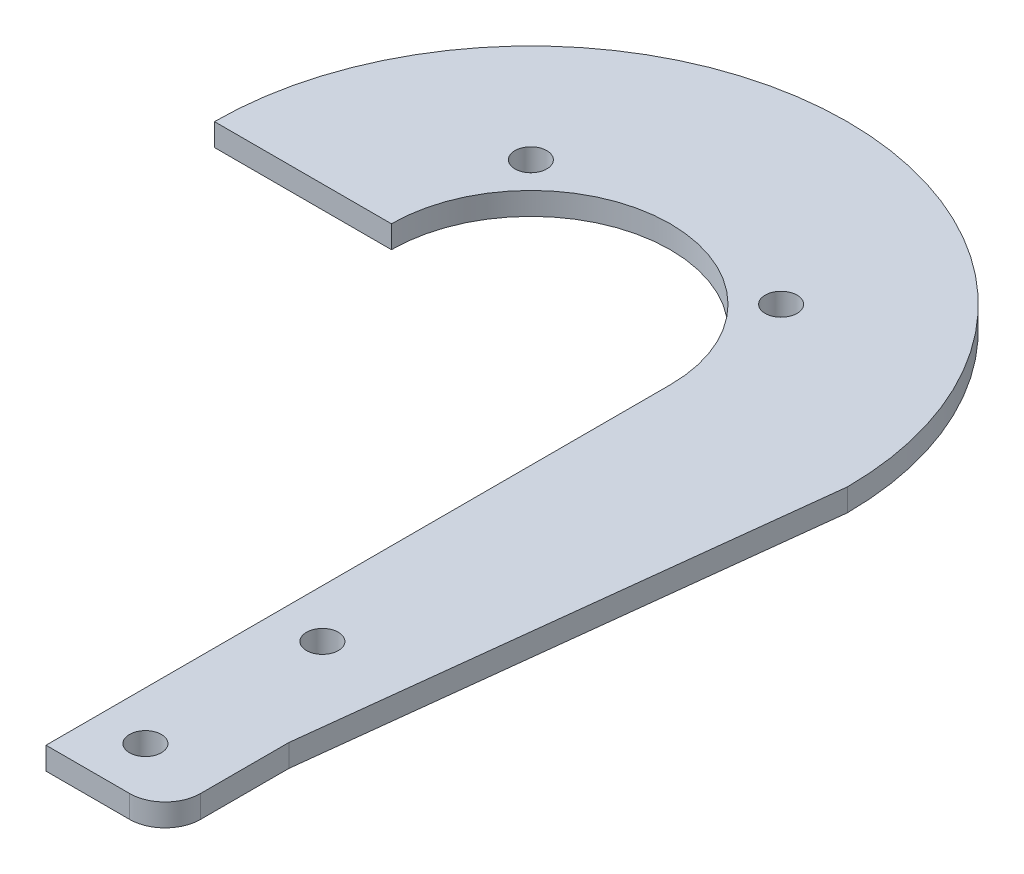
SolidWorks part; units mm, degrees
ref_plane "Front Plane" through (0, 0, 0) normal (0, 0, 1) x (1, 0, 0)
ref_plane "Top Plane" through (0, 0, 0) normal (0, 1, 0) x (1, 0, 0)
ref_plane "Right Plane" through (0, 0, 0) normal (1, 0, 0) x (0, 0, -1)
sketch "Sketch2" plane through (0, 0, 0) normal (0, 1, 0) x (1, 0, 0)
  line L0 (19.7, -88.2) -> (31.525, -88.2)
  line L1 (36.525, -83.2) -> (36.525, -70.7)
  line L2 (19.7, -88.2) -> (19.7, 0)
  line L3 (36.525, -70.7) -> (44.7, 0)
  line L4 (-44.7, 0) -> (-19.7, 0)
  line L5 (26.525, -80.975) -> (26.525, -55.975) construction
  line L6 (0, 0) -> (17.6777, 17.6777) construction
  line L7 (0, 0) -> (-17.6777, 17.6777) construction
  arc A0 (44.7, 0) -> (-44.7, 0) centre (0, 0) ccw
  arc A1 (19.7, 0) -> (-19.7, 0) centre (0, 0) ccw
  circle A2 centre (26.525, -80.975) radius 2.25
  circle A3 centre (26.525, -55.975) radius 2.25
  arc A4 (31.525, -88.2) -> (36.525, -83.2) centre (31.525, -83.2) ccw
  circle A5 centre (-17.6777, 17.6777) radius 2.25
  circle A6 centre (17.6777, 17.6777) radius 2.25
  point P20 (36.525, -88.2)
  dimension "D4" = 4.5
  dimension "D5" = 5
  dimension "D8" = 19.7
  dimension "D9" = 4.5
  dimension "D1" = 16.825
  dimension "D2" = 25
  dimension "D3" = 25
  dimension "D6" = 7.225
  dimension "D7" = 10
  dimension "D10" = 45
  dimension "D11" = 90
  dimension "D12" = 25
  dimension "D13" = 88.2
  dimension "D14" = 17.5
extrude "Boss-Extrude1" add sketch "Sketch2" along normal blind 3.175
